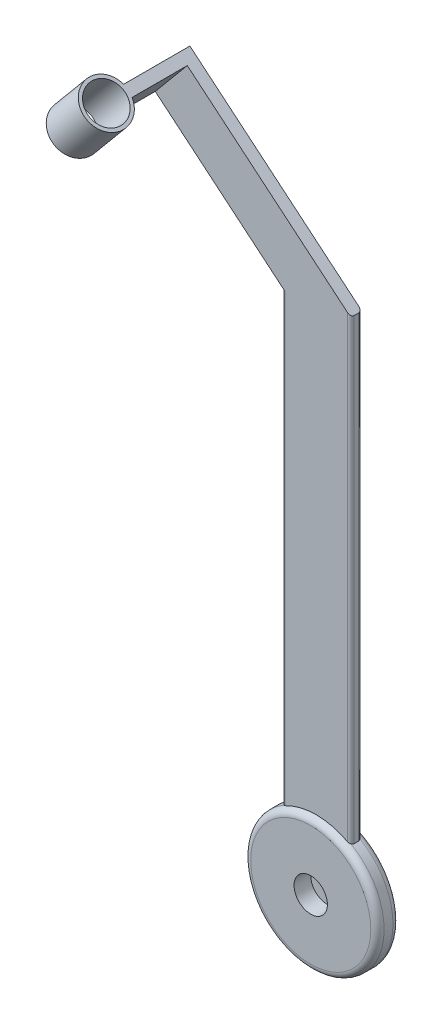
SolidWorks part; units mm, degrees
ref_plane "前视基准面" through (0, 0, 0) normal (0, 0, 1) x (1, 0, 0)
ref_plane "上视基准面" through (0, 0, 0) normal (0, 1, 0) x (1, 0, 0)
ref_plane "右视基准面" through (0, 0, 0) normal (1, 0, 0) x (0, 0, -1)
sketch "草图1" plane through (0, 0, 0) normal (0, 0, 1) x (1, 0, 0)
  circle A0 centre (0, 0) radius 60
  dimension "D1" = 120
extrude "凸台-拉伸1" add sketch "草图1" along normal mid plane 20
sketch "草图2" plane through (0, 0, 10) normal (0, 0, 1) x (1, 0, 0)
  circle A0 centre (0, 0) radius 15
  dimension "D1" = 30
extrude "切除-拉伸1" cut sketch "草图2" against normal blind 15
cosmetic thread "装饰螺纹线1" parameters "D2"=33
sketch "草图3" plane through (0, 0, 0) normal (0, 0, 1) x (1, 0, 0)
  line L0 (0, -82.7002) -> (0, 455.8712) construction
  line L1 (-31, 51.3712) -> (-31, 455.8712)
  line L2 (-31, 455.8712) -> (-152.5229, 557.3162)
  line L3 (-152.5229, 557.3162) -> (-123.6851, 591.8615)
  line L4 (-123.6851, 591.8615) -> (31, 462.7334)
  line L5 (31, 51.3712) -> (31, 455.8712)
  line L6 (0, 455.8712) -> (-152.5229, 583.1944) construction
  line L7 (31, 455.8712) -> (31, 462.7334)
  circle A0 centre (0, 0) radius 60 construction
  arc A1 (31, 51.3712) -> (-31, 51.3712) centre (0, 0) ccw
  dimension "D1" = 404.5
  dimension "D2" = 158.3
  dimension "D3" = 45
  dimension "D4" = 31
extrude "凸台-拉伸2" add sketch "草图3" along normal mid plane 10
sketch "草图5" plane through (0, 0, 5) normal (0, 0, 1) x (1, 0, 0)
  line L0 (-123.6851, 591.8615) -> (-152.5229, 557.3162)
  line L1 (-152.5229, 557.3162) -> (-144.8461, 550.9078)
  line L2 (-152.5229, 557.3162) -> (-31, 455.8712) construction
  line L3 (-144.8461, 550.9078) -> (-116.0083, 585.4531)
  line L4 (31, 462.7334) -> (-123.6851, 591.8615) construction
  line L5 (-116.0083, 585.4531) -> (-123.6851, 591.8615)
  dimension "D1" = 10
extrude "凸台-拉伸3" add sketch "草图5" along normal blind 50
sketch "草图6" plane through (240.3757, 287.9505, 0) normal (0.6408, 0.7677, 0) x (0.7677, -0.6408, 0)
  line L0 (-464.2384, -55) -> (-474.2384, -55) construction
  circle A0 centre (-469.2384, -74) radius 20
  circle A1 centre (-469.2384, -74) radius 17
  point P3 (-469.2384, -55)
  dimension "D1" = 40
  dimension "D2" = 34
  dimension "D3" = 19
extrude "凸台-拉伸4" add sketch "草图6" against normal blind 45
fillet "圆角1" radius 6 2 edges at (60, 0, -10) (60, 0, 10)
fillet "圆角2" radius 3 4 edges at (31, 257.0033, -5) (31, 257.0033, 5) (-31, 253.5722, -5) (-31, 253.5722, 5)
